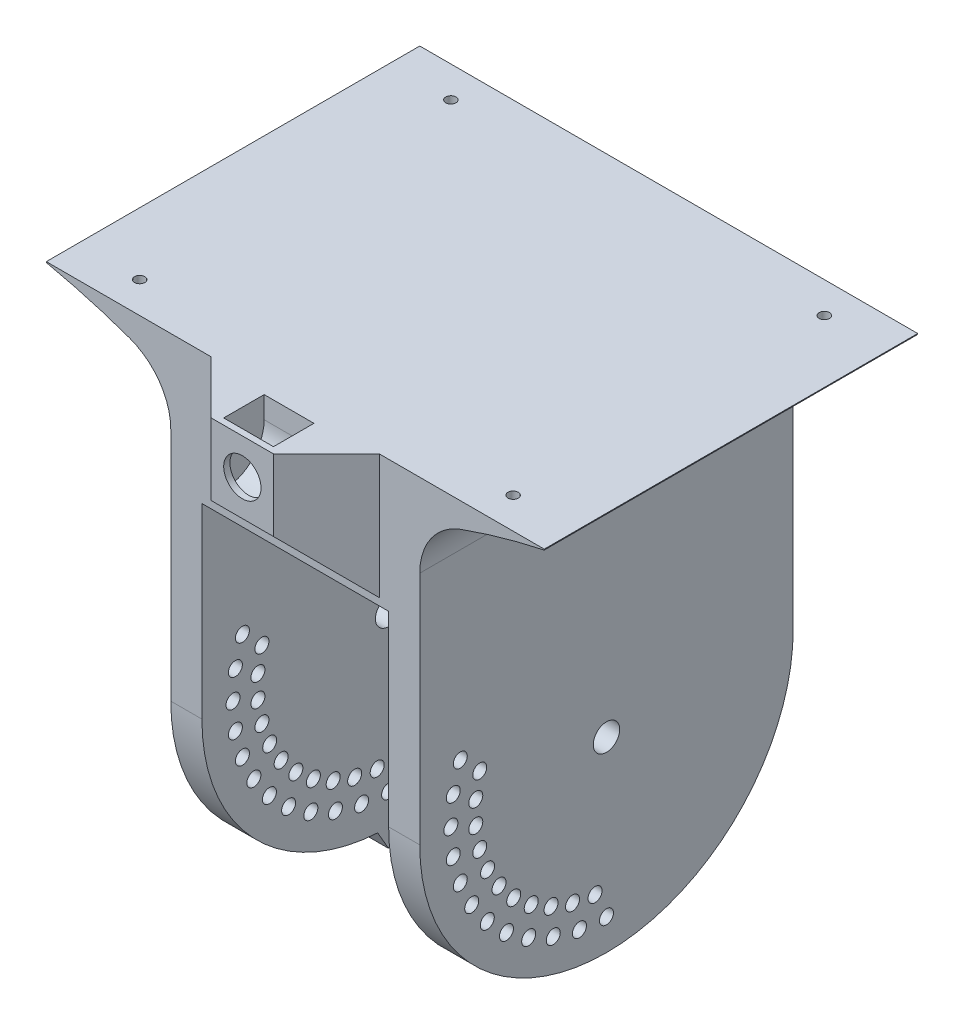
SolidWorks part; units mm, degrees
other "Markup1"
sketch "Sketch9" plane through (-80, -368.8034, 17) normal (-0.4093, -0.7365, 0.5387) x (-0.0783, -0.5598, -0.8249)
ref_plane "Front Plane" through (0, 0, 0) normal (0, 0, 1) x (1, 0, 0)
ref_plane "Top Plane" through (0, 0, 0) normal (0, 1, 0) x (1, 0, 0)
ref_plane "Right Plane" through (0, 0, 0) normal (1, 0, 0) x (0, 0, -1)
sketch "Sketch1" plane through (0, 0, 0) normal (0, 0, 1) x (1, 0, 0)
  line L0 (-27, -206.5) -> (-80, -206.5) construction
  line L1 (-27, -206.5) -> (-80, -206.5)
  line L2 (80, -206.5) -> (-80, -206.5) construction
  line L3 (80, -206.5) -> (-80, -206.5)
  line L4 (80, -206.5) -> (80, -206.7712)
  line L5 (-80, -206.5) -> (-80, -206.7712)
  arc A0 (80.2, -206.7286) -> (225.2451, -153.1407) centre (-32.1304, 320.4019) ccw construction
  arc A1 (80.2, -206.7286) -> (225.2451, -153.1407) centre (-32.1304, 320.4019) ccw
  arc A2 (-225.2451, -153.1407) -> (-80.2, -206.7286) centre (32.1304, 320.4019) ccw construction
  arc A3 (-225.2451, -153.1407) -> (-80.2, -206.7286) centre (32.1304, 320.4019) ccw
  arc A4 (80.2, -206.7286) -> (-80.2, -206.7286) centre (0, 169.6244) cw construction
  arc A5 (-80, -206.7712) -> (80, -206.7712) centre (0, 169.6244) ccw construction
  arc A6 (-80, -206.7712) -> (-51.0096, -215.1963) centre (-122.7938, -408.1138) cw
  arc A7 (80, -206.7712) -> (51.0096, -215.1963) centre (122.7938, -408.1138) ccw
  arc A8 (51.0096, -215.1963) -> (-51.0096, -215.1963) centre (0, -78.1099) cw
  point P13 (-51.0096, -215.1963)
  point P20 (0, 0)
  point P21 (0, 0)
  point P22 (0, 0)
  point P23 (-68.6071, -211.6046)
extrude "Boss-Extrude1" add sketch "Sketch1" against normal up to surface (120 mm away) contours L5 A5 L4 L3 L1
sketch "Sketch2" plane through (0, 0, -120) normal (0, 0, -1) x (-1, 0, 0)
  line L1 (-40, -218.8034) -> (40, -218.8034)
  line L2 (-40, -218.8034) -> (-40, -248.8034)
  line L3 (-40, -248.8034) -> (40, -248.8034)
  line L4 (40, -218.8034) -> (40, -248.8034)
  arc A1 (-51.0096, -215.1963) -> (51.0096, -215.1963) centre (0, -78.1099) ccw construction
  point P4 (0, 0)
  point P7 (0, 0)
  point P8 (46.2922, -257.5156)
  point P9 (0, 0)
  point P13 (0, 0)
  dimension "D1" = 30
  dimension "D2" = 80
extrude "Boss-Extrude2" add sketch "Sketch2" against normal up to surface (120 mm away) up to face at (0, -210.8422, 0)
fillet "Fillet1" radius 20 2 edges at (40, -218.8034, -60) (-40, -218.8034, -60)
sketch "Sketch3" plane through (0, -248.8034, 0) normal (0, -1, 0) x (1, 0, 0)
  line L0 (40, -120) -> (-40, -120) construction
  line L1 (40, 0) -> (30, 0)
  line L2 (40, 0) -> (40, -120)
  line L3 (40, -120) -> (30, -120)
  line L4 (30, 0) -> (30, -120)
  line L5 (40, 0) -> (-40, 0) construction
  line L6 (-40, -120) -> (-30, -120)
  line L7 (-40, -120) -> (-40, 0)
  line L8 (-40, 0) -> (-30, 0)
  line L9 (-30, -120) -> (-30, 0)
  dimension "D1" = 10
extrude "Boss-Extrude3" add sketch "Sketch3" along normal blind 120
fillet "Fillet2" radius 60 4 edges at (35, -368.8034, -120) (35, -368.8034, 0) (-35, -368.8034, 0) (-35, -368.8034, -120)
sketch "Sketch4" plane through (-40, 0, 0) normal (-1, 0, 0) x (0, 0, 1)
  line L0 (-60, -308.8034) -> (-60, -358.8034) construction
  line L1 (-60, -308.8034) -> (-60, -358.8034) construction
  line L2 (-60, -308.8034) -> (-51.3176, -358.0437) construction
  line L3 (-60, -308.8034) -> (-56.3255, -350.8034) construction
  line L4 (-60, -308.8034) -> (-56.3255, -350.8034) construction
  line L5 (-60, -308.8034) -> (-49.0881, -349.5272) construction
  circle A0 centre (-60, -308.8034) radius 4.25
  circle A1 centre (-60, -358.8034) radius 2.25
  circle A2 centre (-51.3176, -358.0437) radius 2.25
  circle A3 centre (-42.899, -355.788) radius 2.25
  circle A4 centre (-35, -352.1046) radius 2.25
  circle A5 centre (-27.8606, -347.1056) radius 2.25
  circle A6 centre (-21.6978, -340.9427) radius 2.25
  circle A7 centre (-16.6987, -333.8034) radius 2.25
  circle A8 centre (-13.0154, -325.9044) radius 2.25
  circle A9 centre (-10.7596, -317.4858) radius 2.25
  circle A10 centre (-10, -308.8034) radius 2.25
  circle A11 centre (-10.7596, -300.1209) radius 2.25
  circle A12 centre (-13.0154, -291.7023) radius 2.25
  circle A13 centre (-56.3255, -350.8034) radius 2.25
  circle A14 centre (-49.0881, -349.5272) radius 2.25
  circle A15 centre (-42.1822, -347.0137) radius 2.25
  circle A16 centre (-35.8178, -343.3392) radius 2.25
  circle A17 centre (-30.1881, -338.6153) radius 2.25
  circle A18 centre (-25.4642, -332.9856) radius 2.25
  circle A19 centre (-21.7897, -326.6211) radius 2.25
  circle A20 centre (-19.2761, -319.7153) radius 2.25
  circle A21 centre (-18, -312.4779) radius 2.25
  circle A22 centre (-18, -305.1288) radius 2.25
  circle A23 centre (-19.2761, -297.8914) radius 2.25
  dimension "D1" = 8.5
  dimension "D2" = 4.5
  dimension "D3" = 50
  dimension "D5" = 10
  dimension "D6" = 5
  dimension "D7" = 42
  dimension "D9" = 10
  dimension "D4" = 12
  dimension "D8" = 11
extrude "Cut-Extrude1" cut sketch "Sketch4" against normal through all
ref_plane "Plane1" through (-10, -206.5, 0) normal (0, 0, -1) x (-1, 0, 0)
sketch "Sketch6" plane through (0, -206.5, 0) normal (0, 1, 0) x (1, 0, 0)
  line L0 (10, -17) -> (10, 0) construction
  line L1 (10, -17) -> (10, 0)
  line L2 (-10, -17) -> (-10, 0) construction
  line L3 (-10, -17) -> (10, -17) construction
  line L4 (80, 120) -> (-80, 120)
  line L5 (-80, 120) -> (-80, 0)
  line L6 (-80, 0) -> (80, 0)
  line L7 (80, 0) -> (80, 120)
  line L10 (-10, 0) -> (10, 0)
  line L12 (-10, -17) -> (-10, 0)
  line L13 (-10, -17) -> (10, -17)
  line L14 (8, -15) -> (-8, -15) construction
  line L15 (-8, -15) -> (-8, -2) construction
  line L16 (-8, -2) -> (8, -2) construction
  line L17 (8, -2) -> (8, -15) construction
  line L18 (8, -15) -> (-8, -15)
  line L19 (-8, -15) -> (-8, -2)
  line L20 (-8, -2) -> (8, -2)
  line L21 (8, -2) -> (8, -15)
  dimension "D1" = 0
extrude "Boss-Extrude4" add sketch "Sketch6" against normal blind 20
sketch "Sketch7" plane through (0, -226.5, 0) normal (0, -1, 0) x (1, 0, 0)
  line L4 (10, 17) -> (-10, 17)
  line L5 (-10, 17) -> (-10, 0)
  line L6 (-10, 0) -> (10, 0)
  line L7 (10, 0) -> (10, 17)
  line L8 (10, 17) -> (-10, 17)
  line L9 (-10, 17) -> (-10, 0)
  line L10 (-10, 0) -> (10, 0)
  line L11 (10, 0) -> (10, 17)
  dimension "D1" = 0
extrude "Boss-Extrude5" add sketch "Sketch7" along normal blind 3
fillet "Fillet3" radius 13 1 edges at (0, -226.5, 2)
sketch "Sketch8" plane through (0, 0, 17) normal (0, 0, 1) x (1, 0, 0)
  line L0 (0, -206.5) -> (0, -229.5) construction
  line L1 (-10, -206.5) -> (10, -206.5) construction
  line L2 (10, -229.5) -> (-10, -229.5) construction
  circle A0 centre (0, -218) radius 6
  point P8 (0, 0)
  dimension "D1" = 12
extrude "Cut-Extrude2" cut sketch "Sketch8" against normal blind 3
chamfer "Chamfer1" distance 17 angle 45 1 edges at (0, -229.5, 0)
sketch "Sketch10" plane through (0, -206.5, 0) normal (0, 1, 0) x (1, 0, 0)
  line L0 (0, 120) -> (0, 0) construction
  line L1 (-80, 120) -> (80, 120) construction
  line L2 (-10, 0) -> (-80, 0) construction
  line L4 (60, 10) -> (-60, 10) construction
  line L5 (60, 10) -> (60, 110) construction
  line L6 (60, 110) -> (-60, 110) construction
  line L7 (-60, 10) -> (-60, 110) construction
  line L8 (60, 10) -> (-60, 110) construction
  line L9 (60, 110) -> (-60, 10) construction
  circle A0 centre (-60, 110) radius 1.65
  circle A1 centre (-60, 10) radius 1.65
  circle A2 centre (60, 10) radius 1.65
  circle A3 centre (60, 110) radius 1.65
  point P9 (0, 60)
  dimension "D3" = 3.3
  dimension "D1" = 100
  dimension "D2" = 120
extrude "Cut-Extrude3" cut sketch "Sketch10" against normal through all
ref_plane "Plane2" through (0, -210.5, 0) normal (0, 1, 0) x (1, 0, 0)
sketch "Sketch11" plane through (0, -210.5, 0) normal (0, 1, 0) x (1, 0, 0)
  circle A0 centre (-60, 110) radius 3
  circle A1 centre (-60, 10) radius 3
  circle A2 centre (60, 110) radius 3
  circle A3 centre (60, 10) radius 3
  dimension "D1" = 6
extrude "Cut-Extrude4" cut sketch "Sketch11" against normal through all
sketch "Sketch13" plane through (-40, 0, 0) normal (-1, 0, 0) x (0, 0, 1)
  line L0 (-60, -1308.8034) -> (-60, 48691.1966) construction
  line L1 (-60, -374.8034) -> (-63.5153, -368.7003)
  line L2 (-63.5153, -368.7003) -> (-60, -366.6755)
  line L3 (-56.4847, -368.7003) -> (-60, -366.6755)
  line L4 (-60, -374.8034) -> (-56.4847, -368.7003)
  arc A0 (-120, -308.8034) -> (-60, -368.8034) centre (-60, -308.8034) ccw construction
  dimension "D1" = 6
extrude "Boss-Extrude6" add sketch "Sketch13" against normal up to surface (10 mm away) up to face at (-30, -325.9044, -10.7654)
chamfer "Chamfer3" distance 17 angle 45 2 edges at (10, -226.5, 0) (-10, -226.5, 0)
